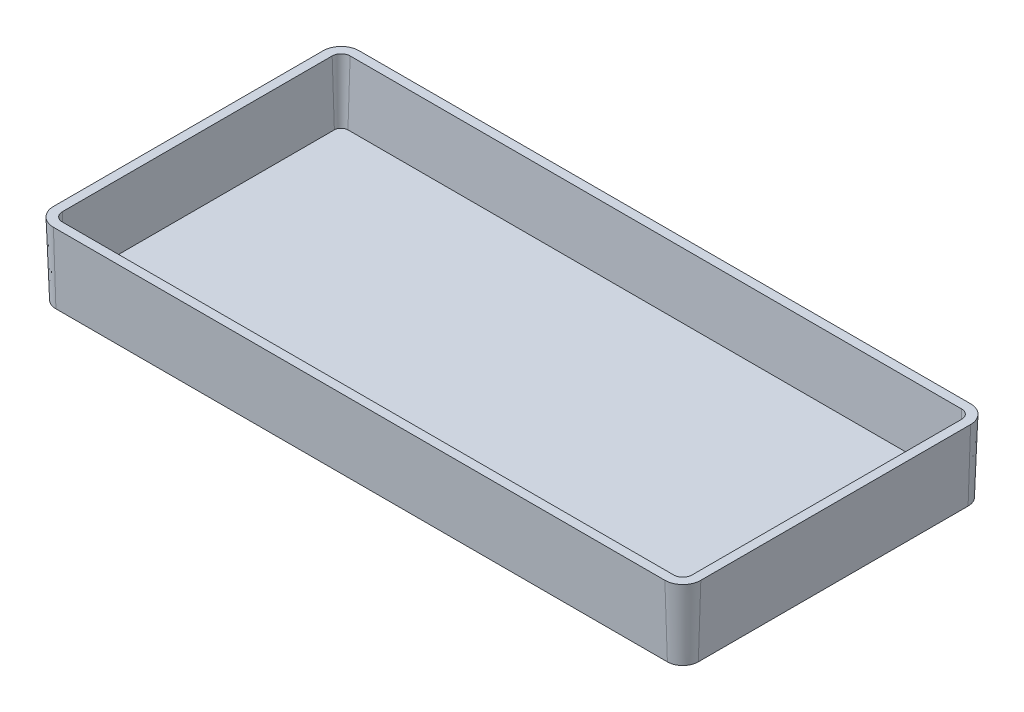
SolidWorks part; units mm, degrees
ref_plane "Front Plane" through (0, 0, 0) normal (0, 0, 1) x (1, 0, 0)
ref_plane "Top Plane" through (0, 0, 0) normal (0, 1, 0) x (1, 0, 0)
ref_plane "Right Plane" through (0, 0, 0) normal (1, 0, 0) x (0, 0, -1)
sketch "Sketch1" plane through (0, 0, 0) normal (0, 1, 0) x (1, 0, 0)
  line L1 (-17, -8.5) -> (17, -8.5)
  line L2 (-18, -7.5) -> (-18, 7.5)
  line L3 (-17, 8.5) -> (17, 8.5)
  line L4 (18, -7.5) -> (18, 7.5)
  line L5 (-18, -8.5) -> (18, 8.5) construction
  line L6 (-18, 8.5) -> (18, -8.5) construction
  arc A0 (-18, 7.5) -> (-17, 8.5) centre (-17, 7.5) cw
  arc A1 (18, 7.5) -> (17, 8.5) centre (17, 7.5) ccw
  arc A2 (18, -7.5) -> (17, -8.5) centre (17, -7.5) cw
  arc A3 (-17, -8.5) -> (-18, -7.5) centre (-17, -7.5) cw
  point P0 (0, 0)
  dimension "D3" = 1
  dimension "D1" = 36
  dimension "D2" = 17
extrude "Boss-Extrude1" add sketch "Sketch1" against normal blind 4 draft 2
shell "Shell1" thickness 0.5 removed face at (0, 0, 0)
